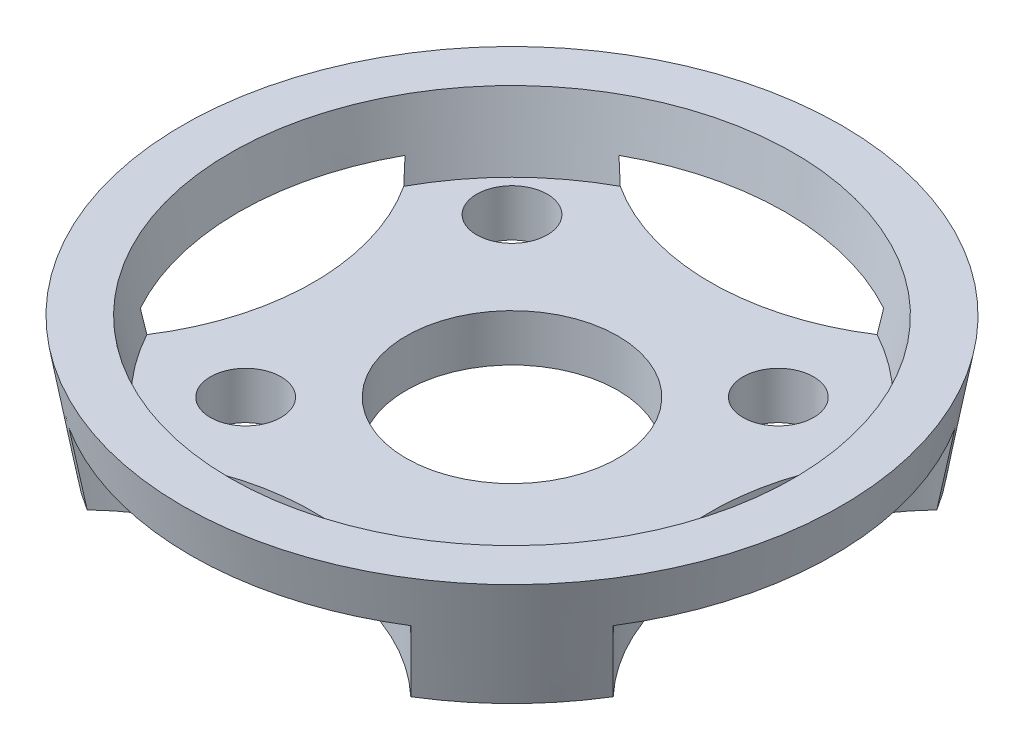
SolidWorks part; units mm, degrees
ref_plane "Ön Düzlem" through (0, 0, 0) normal (0, 0, 1) x (1, 0, 0)
ref_plane "Üst Düzlem" through (0, 0, 0) normal (0, 1, 0) x (1, 0, 0)
ref_plane "Sağ Düzlem" through (0, 0, 0) normal (1, 0, 0) x (0, 0, -1)
sketch "Çizim1" plane through (0, 0, 0) normal (0, 1, 0) x (1, 0, 0)
  circle A0 centre (0, 0) radius 14
  dimension "D1" = 28
extrude "Yükseklik-Ekstrüzyon1" add sketch "Çizim1" along normal blind 5
chamfer "Pah1" distance 5 angle 10 1 edges at (0, 0, 14)
shell "İç Boşaltma1" thickness 2
sketch "Çizim2" plane through (0, 0, 0) normal (0, -1, 0) x (1, 0, 0)
  line L2 (0, 0) -> (0, 17.7286) construction
  circle A0 centre (0, 0) radius 4.5
  arc A2 (-7.5, 11.8216) -> (7.5, 11.8216) centre (0, 18.436) ccw
  arc A3 (11.8216, 7.5) -> (11.8216, -7.5) centre (18.436, 0) ccw
  arc A4 (7.5, -11.8216) -> (-7.5, -11.8216) centre (0, -18.436) ccw
  arc A5 (-11.8216, -7.5) -> (-11.8216, 7.5) centre (-18.436, 0) ccw
  arc A6 (-7.5, -11.8216) -> (7.5, -11.8216) centre (0, 0) ccw
  arc A7 (11.8216, -7.5) -> (11.8216, 7.5) centre (0, 0) ccw
  arc A8 (7.5, 11.8216) -> (-7.5, 11.8216) centre (0, 0) ccw
  circle A10 centre (0, 0) radius 14 construction
  arc A11 (-11.8216, 7.5) -> (-11.8216, -7.5) centre (0, 0) ccw
  point P21 (0, 0)
  point P30 (0, 0)
  dimension "D1" = 9
  dimension "D4" = 10
  dimension "D2" = 15
  dimension "D3" = 4
extrude "Kes-Ekstrüzyon1" cut sketch "Çizim2" against normal blind 3
sketch "Çizim3" plane through (0, 0, 0) normal (0, -1, 0) x (1, 0, 0)
  line L0 (0, 0) -> (-9.0472, 9.0472) construction
  line L1 (0, 2.7039) -> (0, -2.4512) construction
  line L2 (0, 0) -> (-1.7689, -1.7689) construction
  circle A0 centre (-5.6569, 5.6569) radius 1.5
  circle A2 centre (6.7175, 6.7175) radius 1.5
  circle A3 centre (5.6569, -5.6569) radius 1.5
  circle A4 centre (-6.7175, -6.7175) radius 1.5
  point P5 (7.1892, 6.2458)
  point P8 (-6.7175, -6.7175)
  point P17 (0, 0)
  dimension "D2" = 3
  dimension "D6" = 3
  dimension "D1" = 8
  dimension "D4" = 45
  dimension "D3" = 45
  dimension "D5" = 19
extrude "Kes-Ekstrüzyon2" cut sketch "Çizim3" against normal up to next
equation "\"D6@Çizim3\"=\"D2@Çizim3\""
